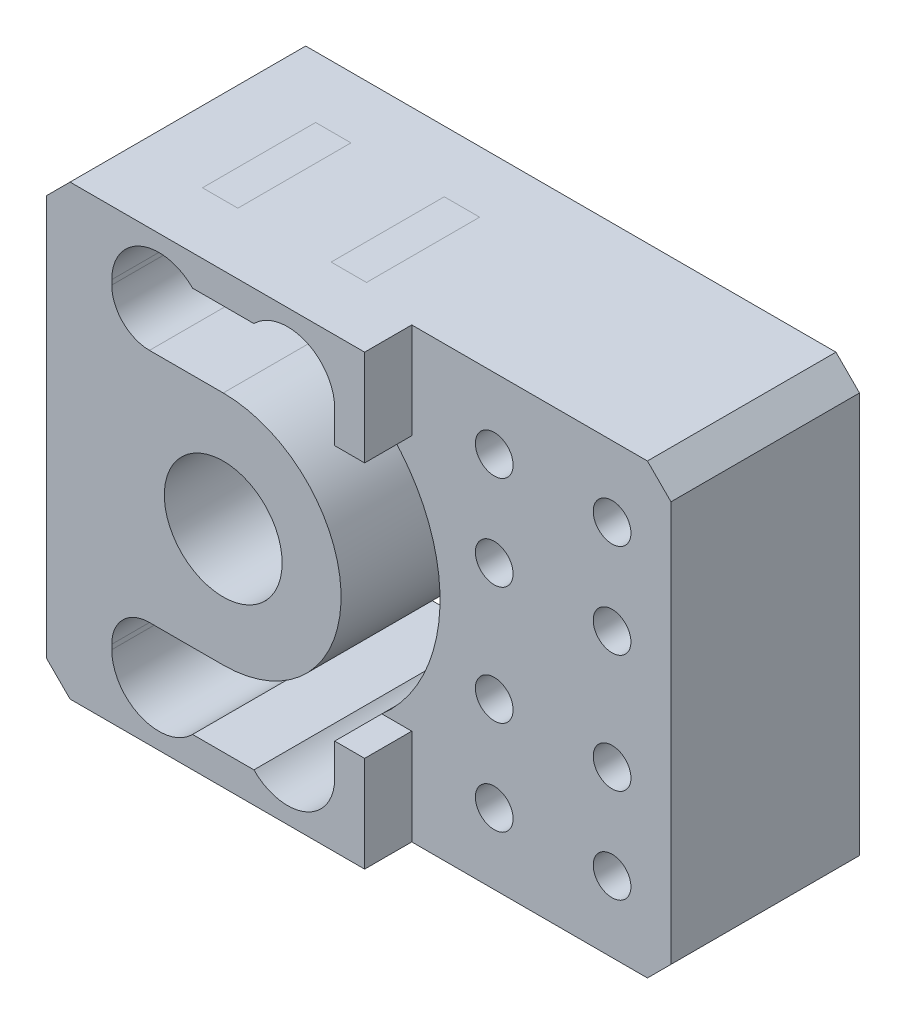
SolidWorks part; units mm, degrees
material "6061 Alloy"
ref_plane "Front Plane" through (0, 0, 0) normal (0, 0, 1) x (1, 0, 0)
ref_plane "Top Plane" through (0, 0, 0) normal (0, 1, 0) x (1, 0, 0)
ref_plane "Right Plane" through (0, 0, 0) normal (1, 0, 0) x (0, 0, -1)
sketch "Sketch1" plane through (0, 0, 0) normal (0, 0, 1) x (1, 0, 0)
  line L1 (7.5, -9.5) -> (-7.5, -9.5)
  line L2 (7.5, -9.5) -> (7.5, 9.5)
  line L3 (7.5, 9.5) -> (-7.5, 9.5)
  line L4 (-7.5, -9.5) -> (-7.5, 9.5)
  line L5 (7.5, -9.5) -> (-7.5, 9.5) construction
  line L6 (7.5, 9.5) -> (-7.5, -9.5) construction
  point P0 (0, 0)
  dimension "D1" = 19
  dimension "D2" = 15
extrude "Boss-Extrude1" add sketch "Sketch1" along normal blind 5 and the other way blind 5
sketch "Sketch2" plane through (0, 0, 0) normal (0, 0, 1) x (1, 0, 0)
  line L1 (-2.73, 8.8) -> (-2.73, 9.5) construction
  line L2 (7.5, 9.5) -> (-7.5, 9.5) construction
  line L3 (0, 0) -> (0, -5.2202) construction
  circle A0 centre (-2.73, 6.8) radius 2
  dimension "D2" = 5.46
  dimension "D1" = 2.7
  dimension "D3" = 4
extrude "Cut-Extrude1" cut sketch "Sketch2" against normal blind 6 and the other way blind 10
mirror "Mirror3" about plane through (0, 0, 0) normal (0, 1, 0) of "Cut-Extrude1"
sketch "Sketch5" plane through (0, 0, 0) normal (0, 0, 1) x (1, 0, 0)
  line L0 (0, 0) -> (0, 8.2078) construction
  circle A0 centre (2.73, 6.8) radius 2
  circle A1 centre (-2.73, 6.8) radius 2 construction
  point P2 (-2.73, 6.8)
extrude "Cut-Extrude4" cut sketch "Sketch5" against normal blind 17 and the other way blind 17
sketch "Sketch6" plane through (0, 0, 0) normal (0, 0, 1) x (1, 0, 0)
  circle A0 centre (2.73, -6.8) radius 2
  circle A3 centre (2.73, 6.8) radius 2 construction
  point P5 (-2.73, -6.8)
  point P6 (2.73, 6.8)
extrude "Cut-Extrude5" cut sketch "Sketch6" against normal blind 17 and the other way blind 17
sketch "Sketch10" plane through (0, 0, 0) normal (0, 0, 1) x (1, 0, 0)
  line L0 (-0.73, 6.8) -> (-4.73, 6.8) construction
  line L1 (4.73, -6.8) -> (-4.73, -6.8)
  line L2 (4.73, -6.8) -> (4.73, 6.8)
  line L3 (4.73, 6.8) -> (-4.73, 6.8)
  line L4 (-4.73, -6.8) -> (-4.73, 6.8)
  line L5 (4.73, -6.8) -> (-4.73, 6.8) construction
  line L6 (4.73, 6.8) -> (-4.73, -6.8) construction
  circle A0 centre (-2.73, 6.8) radius 2 construction
  point P0 (0, 0)
extrude "Cut-Extrude6" cut sketch "Sketch10" against normal through all and the other way through all
sketch "Sketch7" plane through (0, 0, 0) normal (0, 0, 1) x (1, 0, 0)
  circle A0 centre (0, 0) radius 2.5
  circle A1 centre (0, 0) radius 5
  dimension "D1" = 10
  dimension "D2" = 5
extrude "Boss-Extrude2" add sketch "Sketch7" along normal up to surface (5 mm away) and the other way up to surface (5 mm away) separate body up to face at (0, 0, 5) other way up to face at (0, 0, -5)
sketch "Sketch8" plane through (0, 0, 0) normal (0, 0, 1) x (1, 0, 0)
  line L0 (0, 5) -> (-7.5, 5)
  line L1 (-7.5, 5) -> (-7.5, 0)
  line L2 (-7.5, 0) -> (-5, 0)
  line L3 (-5, 0) -> (0, 5)
  line L4 (-7.5, 9.5) -> (-7.5, -9.5) construction
  circle A0 centre (0, 0) radius 5 construction
extrude "Boss-Extrude3" add sketch "Sketch8" along normal up to surface (5 mm away) and the other way up to surface (5 mm away) up to face at (0, 0, 5) other way up to face at (0, 0, -5)
mirror "Mirror7" about plane through (0, 0, 0) normal (0, 1, 0) of "Boss-Extrude3"
fillet "Fillet1" radius 1.6 2 edges at (-4.73, -5, 0) (-4.73, 5, 0)
sketch "Sketch11" plane through (0, 0, 5) normal (0, 0, 1) x (1, 0, 0)
  line L0 (7.5, 9.5) -> (-7.5, 9.5) construction
  line L1 (4.73, 9.5) -> (17, 9.5)
  line L2 (4.73, 9.5) -> (4.73, -9.5)
  line L3 (4.73, -9.5) -> (17, -9.5)
  line L4 (17, 9.5) -> (17, -9.5)
  line L5 (-7.5, -9.5) -> (7.5, -9.5) construction
  line L6 (4.73, -6.8) -> (4.73, -1.6208) construction
  dimension "D1" = 17
extrude "Boss-Extrude4" add sketch "Sketch11" against normal up to surface (10 mm away) up to face at (-0.365, -6.2309, -5)
chamfer "Chamfer1" distance 1 angle 45 4 edges at (-7.5, -9.5, 0) (17, -9.5, 0) (17, 9.5, 0) (-7.5, 9.5, 0)
sketch "Sketch16" plane through (0, 0, 5) normal (0, 0, 1) x (1, 0, 0)
  line L1 (-3.13, 5) -> (2.6756, 5)
  line L2 (-3.13, 5) -> (-3.13, 8.2)
  line L3 (-3.13, 8.2) -> (2.6756, 8.2)
  line L4 (2.6756, 5) -> (2.6756, 8.2)
  dimension "D1" = 3.2
extrude "Cut-Extrude8" cut sketch "Sketch16" against normal blind 11.5
mirror "Mirror8" about plane through (0, 0, 0) normal (0, 1, 0) of "Cut-Extrude8"
sketch "Sketch17" plane through (0, 0, 5) normal (0, 0, 1) x (1, 0, 0)
  line L0 (0, 0) -> (11.815, 0) construction
  arc A0 (3.2674, -5.1511) -> (3.2674, 5.1511) centre (0, 0) ccw construction
  arc A1 (0, -5) -> (4.73, -1.6208) centre (0, 0) ccw construction
  arc A2 (2.6782, -4.2223) -> (2.6782, 4.2223) centre (0, 0) ccw
  arc A3 (3.8566, -6.08) -> (3.8566, 6.08) centre (0, 0) ccw
  arc A4 (2.6782, -4.2223) -> (3.8566, -6.08) centre (3.2674, -5.1511) ccw
  arc A5 (2.6782, 4.2223) -> (3.8566, 6.08) centre (3.2674, 5.1511) cw
  arc A6 (4.73, 1.6208) -> (0, 5) centre (0, 0) ccw construction
  dimension "D1" = 1.1
  dimension "D3" = 1.1
extrude "Cut-Extrude9" cut sketch "Sketch17" against normal blind 11.5
sketch "Sketch18" plane through (0, 0, 0) normal (0, 1, 0) x (1, 0, 0)
  line L0 (-2.73, -5) -> (-2.73, 5) construction
  line L1 (-1.98, -2.4) -> (-3.48, -2.4)
  line L2 (-1.98, -2.4) -> (-1.98, 2.4)
  line L3 (-1.98, 2.4) -> (-3.48, 2.4)
  line L4 (-3.48, -2.4) -> (-3.48, 2.4)
  line L5 (-1.98, -2.4) -> (-3.48, 2.4) construction
  line L6 (-1.98, 2.4) -> (-3.48, -2.4) construction
  point P0 (-2.73, 0)
  dimension "D1" = 4.8
  dimension "D2" = 1.5
split line "Split Line1"
split line "Split Line2"
sketch "Sketch18<2>" plane through (0, 0, 0) normal (0, 1, 0) x (1, 0, 0) same geometry as "Sketch18"
sketch "Sketch19" plane through (0, 0, 0) normal (0, 1, 0) x (1, 0, 0)
  line L0 (2.73, -5) -> (2.73, 5) construction
  line L1 (3.48, -2.4) -> (1.98, -2.4)
  line L2 (3.48, -2.4) -> (3.48, 2.4)
  line L3 (3.48, 2.4) -> (1.98, 2.4)
  line L4 (1.98, -2.4) -> (1.98, 2.4)
  line L5 (3.48, -2.4) -> (1.98, 2.4) construction
  line L6 (3.48, 2.4) -> (1.98, -2.4) construction
  line L7 (-3.48, 2.4) -> (-1.98, 2.4) construction
  line L8 (-3.48, -2.4) -> (-3.48, 2.4) construction
  point P0 (2.73, 0)
split line "Split Line4"
split line "Split Line5"
sketch "Sketch19<3>" plane through (0, 0, 0) normal (0, 1, 0) x (1, 0, 0) same geometry as "Sketch19"
hole_wizard "Trou taraudé M21" positions "Sketch23" profile "Sketch22" tap size "M2" standard "Iso" end condition through all
sketch "Sketch23" plane through (0, 0, 5) normal (0, 0, 1) x (1, 0, 0)
  line L0 (0, 0) -> (16.8835, 0) construction
  line L4 (9.5, -6.5) -> (14.5, -6.5)
  line L5 (9.5, -6.5) -> (9.5, 6.5)
  line L6 (9.5, 6.5) -> (14.5, 6.5)
  line L7 (14.5, -6.5) -> (14.5, 6.5)
  line L8 (9.5, -6.5) -> (14.5, 6.5) construction
  line L9 (9.5, 6.5) -> (14.5, -6.5) construction
  line L10 (12, -6.5) -> (12, 0) construction
  line L11 (16, 9.5) -> (-6.5, 9.5) construction
  point P0 (14.5, 6.5)
  point P1 (14.5, -6.5)
  point P13 (9.5, 6.5)
  point P15 (9.5, -6.5)
  point P158 (9.5, 2.5)
  point P160 (14.5, 2.5)
  point P162 (14.5, -2.5)
  point P164 (9.5, -2.5)
  dimension "D1" = 3
  dimension "D2" = 12
  dimension "D3" = 5
  dimension "D4" = 5
sketch "Sketch22" plane through (14.5, 6.5, 5) normal (1, 0, 0) x (0, -1, 0)
  line L0 (0, 0) -> (0, 10)
  line L1 (0, 10) -> (0.8, 10)
  line L2 (0.8, 10) -> (0.8, 0)
  line L5 (0.8, 0) -> (0, 0)
  line L11 (0, -6.35) -> (0, 107.95) construction
  dimension "Diamètre du trou pour taraudage jusqu'au prochain" = 1.6
  dimension "Profondeur du trou pour taraudage jusqu'au prochain" = 10
cosmetic thread "Filetage de perçage2" parameters "D2"=2
cosmetic thread "Filetage de perçage3" parameters "D2"=2
cosmetic thread "Filetage de perçage4" parameters "D2"=2
cosmetic thread "Filetage de perçage5" parameters "D2"=2
cosmetic thread "Filetage de perçage6" parameters "D2"=2
cosmetic thread "Filetage de perçage7" parameters "D2"=2
cosmetic thread "Filetage de perçage8" parameters "D2"=2
cosmetic thread "Filetage de perçage9" parameters "D2"=2
sketch "Sketch24" plane through (0, 0, 5) normal (0, 0, 1) x (1, 0, 0)
  line L0 (16, 9.5) -> (-6.5, 9.5) construction
  line L1 (6, 9.5) -> (17, 9.5)
  line L2 (6, 9.5) -> (6, -9.5)
  line L3 (6, -9.5) -> (17, -9.5)
  line L4 (17, 9.5) -> (17, -9.5)
  line L5 (6, 9.5) -> (17, -9.5) construction
  line L6 (6, -9.5) -> (17, 9.5) construction
  line L7 (17, -8.5) -> (17, 8.5) construction
  line L8 (-6.5, -9.5) -> (16, -9.5) construction
  point P0 (11.5, 0)
  dimension "D1" = 11
extrude "Cut-Extrude10" cut sketch "Sketch24" against normal blind 2
sketch "Sketch25" plane through (0, 0, 5) normal (0, 0, 1) x (1, 0, 0)
  line L0 (17, -8.5) -> (17, 8.5) construction
  line L1 (17, -5.4284) -> (4.73, -5.4284)
  line L2 (17, -5.4284) -> (17, 5.4284)
  line L3 (17, 5.4284) -> (4.73, 5.4284)
  line L5 (17, -5.4284) -> (4.73, 5.4284) construction
  line L6 (17, 5.4284) -> (4.73, -5.4284) construction
  line L7 (4.73, 5.4284) -> (6.865, 0)
  line L8 (6.865, 0) -> (4.73, -5.4284)
  point P0 (10.865, 0)
  dimension "D1" = 4
extrude "Cut-Extrude11" cut sketch "Sketch25" against normal up to surface (2 mm away) up to face at (10.3, -2.5, 3)
sketch "Sketch26" plane through (0, 0, 5) normal (0, 0, 1) x (1, 0, 0)
  line L0 (17, -8.5) -> (17, 8.5) construction
  line L1 (17, -4) -> (5.9867, -4)
  line L2 (17, -4) -> (17, 4)
  line L3 (17, 4) -> (5.9867, 4)
  line L4 (5.9867, -4) -> (5.9867, 4)
  line L5 (17, -4) -> (5.9867, 4) construction
  line L6 (17, 4) -> (5.9867, -4) construction
  arc A0 (4.73, -5.4284) -> (4.73, 5.4284) centre (0, 0) ccw construction
  point P0 (11.4933, 0)
  dimension "D1" = 8
hole_wizard "Trou taraudé M2.51" positions "Sketch31" profile "Sketch30" tap size "M2.5" standard "Iso"
sketch "Sketch31" plane through (-7.5, 0, 0) normal (-1, 0, 0) x (0, 0, 1)
  point P0 (0, 0)
sketch "Sketch30" plane through (-7.5, 0, 0) normal (0, 1, 0) x (0, 0, 1)
  line L0 (0, 0) -> (0, 8.8659)
  line L1 (0, 8.8659) -> (1.025, 8.25)
  line L2 (1.025, 8.25) -> (1.025, 0)
  line L5 (1.025, 0) -> (0, 0)
  line L10 (0, 8.8659) -> (-1.025, 8.25) construction
  line L11 (0, -6.35) -> (0, 107.95) construction
  dimension "Diamètre du trou pour taraudage" = 2.05
  dimension "Profondeur du trou pour taraudage" = 8.25
  dimension "Angle de pointe" = 118
cosmetic thread "Filetage de perçage1" parameters "D1"=5.2198, "D2"=2.5
sketch "Sketch32" plane through (0, 0, 3) normal (0, 0, 1) x (1, 0, 0)
  line L0 (16, 9.5) -> (6, 9.5) construction
  line L1 (4.6035, 7.5) -> (7.2, 7.5)
  line L2 (4.6035, 7.5) -> (4.6035, 2.4508)
  line L3 (4.6035, 2.4508) -> (7.2, 2.4508)
  line L4 (7.2, 7.5) -> (7.2, 2.4508)
  arc A2 (4.73, 6.8) -> (1.3017, 8.2) centre (2.73, 6.8) ccw construction
  arc A3 (4.73, -5.4284) -> (4.73, 5.4284) centre (0, 0) ccw construction
  dimension "D1" = 2
extrude "Cut-Extrude12" [suppressed] cut sketch "Sketch32" against normal blind 10 and the other way blind 10
mirror "Mirror9" [suppressed] about plane through (0, 0, 0) normal (0, 1, 0)
sketch "Sketch33" [suppressed] plane through (0, 0, 3) normal (0, 0, 1) x (1, 0, 0)
  line L0 (7.2, 7.5) -> (7.2, 2.4508) construction
  line L1 (7.2, 3.4223) -> (5.8187, 3.4223)
  line L2 (7.2, 3.4223) -> (7.2, -3.0584)
  line L3 (7.2, -3.0584) -> (5.8187, -3.0584)
  line L4 (5.8187, 3.4223) -> (5.8187, -3.0584)
extrude "Cut-Extrude13" [suppressed] cut sketch "Sketch33" against normal blind 10
fillet "Fillet2" [suppressed] radius 2
